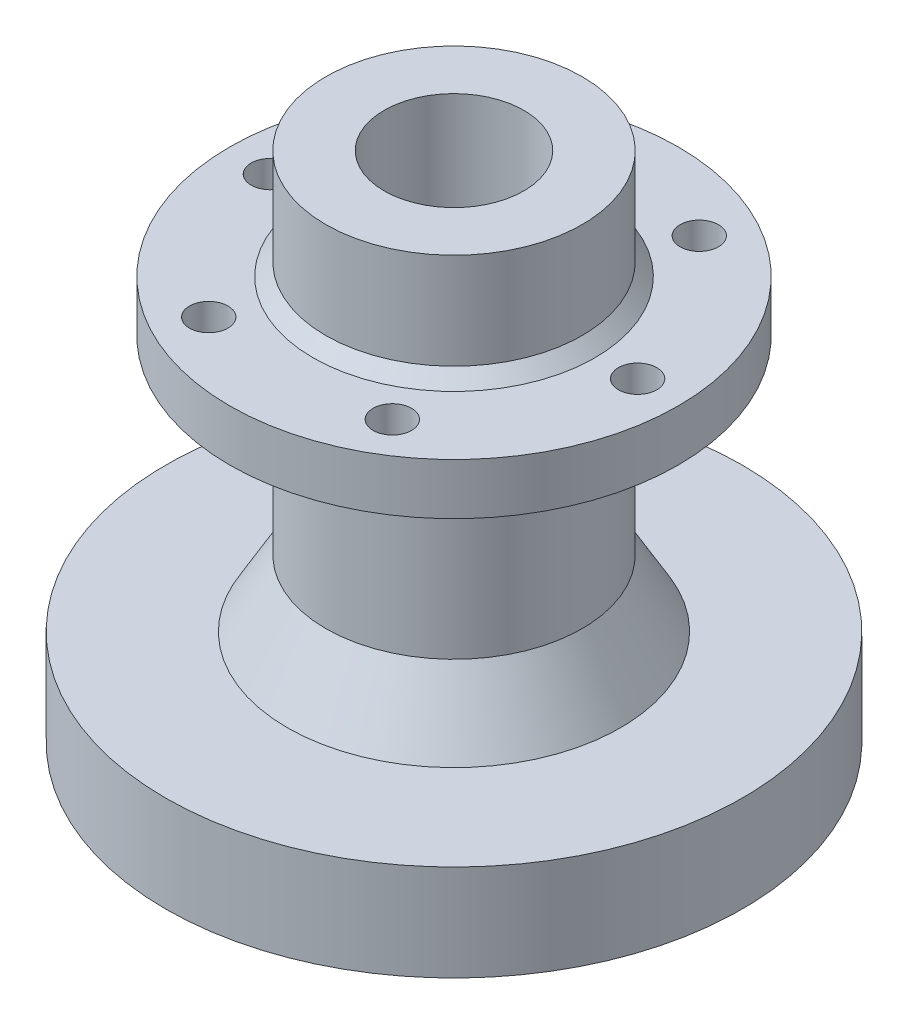
SolidWorks part; units mm, degrees
ref_plane "Спереди" through (0, 0, 0) normal (0, 0, 1) x (1, 0, 0)
ref_plane "Сверху" through (0, 0, 0) normal (0, 1, 0) x (1, 0, 0)
ref_plane "Справа" through (0, 0, 0) normal (1, 0, 0) x (0, 0, -1)
sketch "Эскиз1" plane through (0, 0, 0) normal (0, 1, 0) x (1, 0, 0)
  line L0 (-2, -6.7082) -> (-2, -8.85)
  line L1 (-2, -8.85) -> (2.5, -8.85)
  line L2 (2.5, -8.85) -> (2.5, -6.5383)
  circle A0 centre (0, 0) radius 45
  arc A1 (2.5, -6.5383) -> (-2, -6.7082) centre (0, 0) ccw
  dimension "D1" = 4.5
extrude "Вытянуть1" add sketch "Эскиз1" along normal blind 15
sketch "Эскиз2" plane through (0, 15, 0) normal (0, 1, 0) x (1, 0, 0)
  circle A0 centre (0, 0) radius 20
extrude "Вытянуть2" add sketch "Эскиз2" along normal blind 65
sketch "Эскиз4" plane through (0, 80, 0) normal (0, 1, 0) x (1, 0, 0)
  circle A0 centre (0, 0) radius 10.9
extrude "Вытянуть4" cut sketch "Эскиз4" against normal blind 52
ref_plane "Плоскость1" through (0, 55, 0) normal (0, 1, 0) x (-1, 0, 0)
sketch "Эскиз5" plane through (0, 55, 0) normal (0, 1, 0) x (-1, 0, 0)
  circle A0 centre (0, 0) radius 35
  circle A1 centre (0, 0) radius 10.9
extrude "Вытянуть5" add sketch "Эскиз5" along normal blind 8
chamfer "Фаска3" distance 2 angle 45 2 edges at (0, 55, 20) (0, 63, 20)
chamfer "Фаска4" distance 6 angle 60 1 edges at (0, 15, 20) first distance on face at (0, 15, 45)
sketch "Эскиз6" plane through (0, 15, 0) normal (0, -1, 0) x (1, 0, 0)
  circle A0 centre (0, 0) radius 7
extrude "Вытянуть8" cut sketch "Эскиз6" against normal blind 4
sketch "Эскиз7" plane through (0, 63, 0) normal (0, 1, 0) x (1, 0, 0)
  circle A0 centre (-28.1542, -0.4999) radius 3
  circle A1 centre (-14.51, 24.1323) radius 3
  circle A2 centre (13.6441, 24.6322) radius 3
  circle A3 centre (28.1542, 0.4999) radius 3
  circle A4 centre (14.51, -24.1323) radius 3
  circle A5 centre (-13.6441, -24.6322) radius 3
extrude "Вырез-Вытянуть1" cut sketch "Эскиз7" against normal up to next
